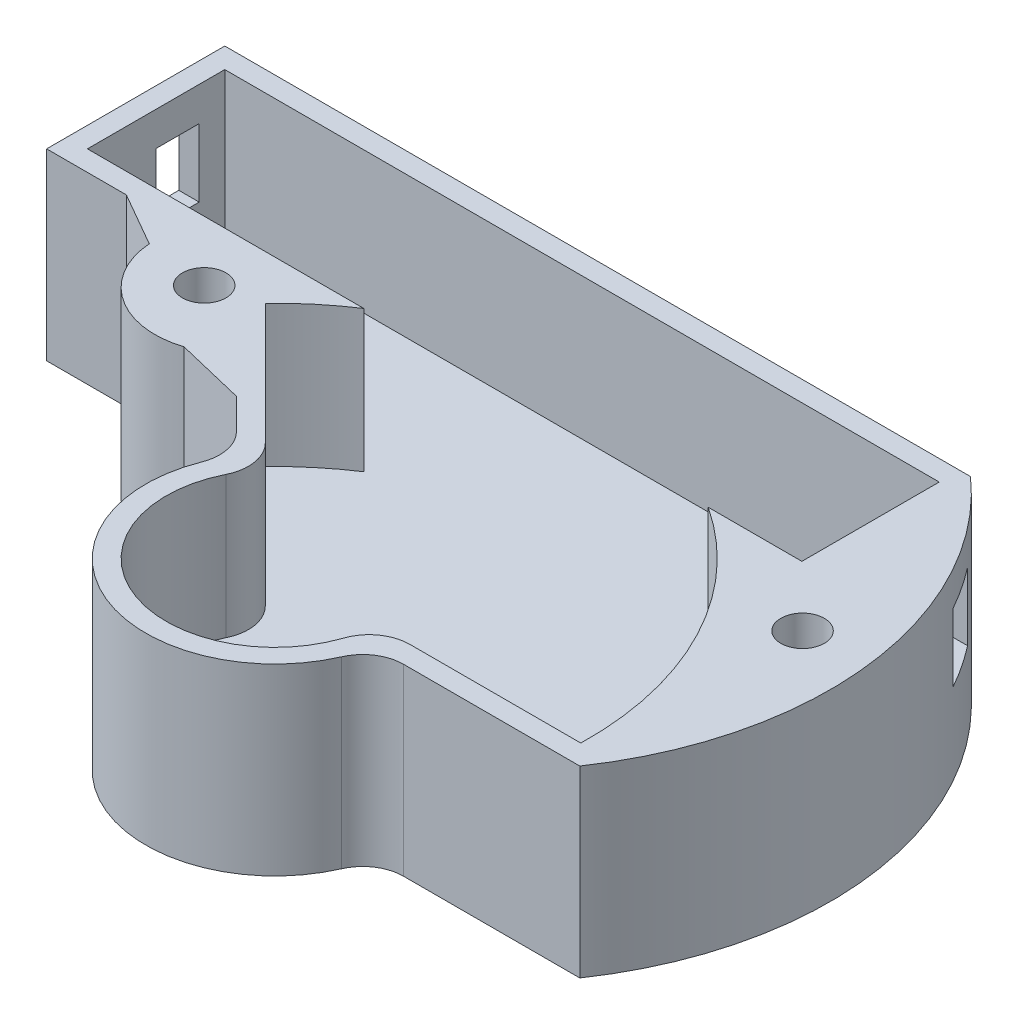
SolidWorks part; units mm, degrees
ref_plane "Alzado" through (0, 0, 0) normal (0, 0, 1) x (1, 0, 0)
ref_plane "Planta" through (0, 0, 0) normal (0, 1, 0) x (1, 0, 0)
ref_plane "Vista lateral" through (0, 0, 0) normal (1, 0, 0) x (0, 0, -1)
sketch "Croquis1" plane through (0, 0, 0) normal (0, 1, 0) x (1, 0, 0)
  line L0 (-35, 32.5) -> (35, -32.5) construction
  line L1 (-35, 32.5) -> (35, 32.5)
  line L2 (-35, 32.5) -> (-35, -32.5)
  line L3 (-35, -32.5) -> (35, -32.5)
  line L4 (35, 32.5) -> (35, -32.5)
  dimension "D1" = 70
  dimension "D2" = 65
extrude "Extruir1" add sketch "Croquis1" along normal blind 3.5
sketch "Croquis2" plane through (0, 3.5, 0) normal (0, 1, 0) x (1, 0, 0)
  line L0 (0, 32.5) -> (0, -32.5) construction
  line L1 (35, 32.5) -> (-35, 32.5) construction
  line L2 (-35, -32.5) -> (35, -32.5) construction
  circle A0 centre (0, -17.5) radius 3.1
  dimension "D1" = 6.2
  dimension "D2" = 15
extrude "Extruir2" cut sketch "Croquis2" against normal blind 5
sketch "Croquis3" plane through (0, 3.5, 0) normal (0, 1, 0) x (1, 0, 0)
  line L0 (0, -32.5) -> (0, 32.5) construction
  line L1 (-35, -32.5) -> (35, -32.5) construction
  line L2 (35, 32.5) -> (-35, 32.5) construction
  line L3 (-32.9868, -32.5) -> (-32.9868, 32.5) construction
  line L4 (-32.9868, 1.7) -> (-12.6633, 1.7)
  line L5 (18.8496, -32.5) -> (18.8496, 32.5) construction
  line L6 (-32.9868, 3.5) -> (18.8496, 3.5) construction
  line L7 (-32.9868, 2) -> (0, 2) construction
  line L8 (-32.9868, 11.5) -> (18.8496, 11.5) construction
  line L9 (0, -17.5) -> (-14.8492, -2.6508) construction
  line L10 (0, -17.5) -> (14.8492, -2.6508) construction
  line L11 (0, 2) -> (18.8496, 2) construction
  line L12 (-32.9868, 2) -> (18.8496, 2) construction
  line L13 (-32.9868, 11.8) -> (18.8496, 11.8)
  line L14 (-5.3033, -12.1967) -> (-16.2635, -1.2365) construction
  line L15 (12.6633, 1.7) -> (18.8496, 1.7)
  line L16 (-32.9868, 1.7) -> (18.8496, 1.7) construction
  line L17 (7.9844, -18) -> (22.9946, -18)
  line L18 (-5.9993, -12.2078) -> (-16.6132, -1.5939)
  line L19 (0, -17.5) -> (23, -17.5) construction
  line L20 (7.5, -17.5) -> (23, -17.5) construction
  line L21 (-5.6569, -12.5503) -> (-16.617, -1.5901) construction
  line L22 (7.5, -18) -> (23, -18) construction
  line L23 (-32.9868, 11.8) -> (-32.9868, 1.7)
  line L24 (18.8496, 11.8) -> (18.8496, 1.7)
  line L25 (-34.4868, 13.3) -> (20.3496, 13.3)
  line L26 (20.3496, 13.3) -> (20.3496, 0.2)
  line L27 (16.9399, 0.2) -> (20.3496, 0.2)
  line L28 (9.2871, -19.5) -> (24.4182, -19.5)
  line L29 (-7.9812, -12.3473) -> (-18.6805, -1.6479)
  line L30 (-34.4868, 0.2) -> (-16.9399, 0.2)
  line L31 (-34.4868, 13.3) -> (-34.4868, 0.2)
  circle A0 centre (0, -17.5) radius 21 construction
  circle A1 centre (0, -17.5) radius 7.5 construction
  arc A2 (-12.6633, 1.7) -> (-16.6132, -1.5939) centre (0, -17.5) ccw
  circle A3 centre (0, -17.5) radius 23 construction
  arc A4 (-5.9993, -12.2078) -> (7.9844, -18) centre (0, -17.5) ccw
  arc A5 (22.9946, -18) -> (12.6633, 1.7) centre (0, -17.5) ccw
  arc A6 (24.4182, -19.5) -> (16.9399, 0.2) centre (0, -17.5) ccw
  arc A7 (-7.9812, -12.3473) -> (9.2871, -19.5) centre (0, -17.5) ccw
  arc A8 (-16.9399, 0.2) -> (-18.6805, -1.6479) centre (0, -17.5) ccw
  dimension "D3" = 42
  dimension "D8" = 15
  dimension "D9" = 46
  dimension "D14" = 0.5
  dimension "D2" = 51.8364
  dimension "D6" = 90
  dimension "D7" = 45
  dimension "D1" = 32.9868
  dimension "D4" = 1.5
  dimension "D5" = 9.5
  dimension "D10" = 1.8
  dimension "D11" = 0.3
  dimension "D12" = 0.5
  dimension "D13" = 0.5
  dimension "D15" = 1.5
extrude "Extruir3" add sketch "Croquis3" along normal blind 10
sketch "Croquis4" plane through (0, 3.5, 0) normal (0, 1, 0) x (1, 0, 0)
  line L0 (-34.4868, 0.2) -> (-16.9399, 0.2) construction
  line L1 (-34.4868, 13.3) -> (-34.4868, 0.2) construction
  line L2 (20.3496, 13.3) -> (-34.4868, 13.3) construction
  line L3 (20.3496, 0.2) -> (20.3496, 13.3) construction
  line L4 (16.9399, 0.2) -> (20.3496, 0.2) construction
  line L5 (9.2871, -19.5) -> (24.4182, -19.5) construction
  line L6 (-18.6805, -1.6479) -> (-7.9812, -12.3473) construction
  line L7 (-34.4868, 0.2) -> (-16.9399, 0.2)
  line L8 (-34.4868, 13.3) -> (-34.4868, 0.2)
  line L9 (20.3496, 13.3) -> (-34.4868, 13.3)
  line L10 (20.3496, 0.2) -> (20.3496, 13.3)
  line L11 (16.9399, 0.2) -> (20.3496, 0.2)
  line L12 (9.2871, -19.5) -> (24.4182, -19.5)
  line L13 (-18.6805, -1.6479) -> (-7.9812, -12.3473)
  arc A0 (-16.9399, 0.2) -> (-18.6805, -1.6479) centre (0, -17.5) ccw construction
  arc A1 (24.4182, -19.5) -> (16.9399, 0.2) centre (0, -17.5) ccw construction
  arc A2 (-7.9812, -12.3473) -> (9.2871, -19.5) centre (0, -17.5) ccw construction
  arc A3 (-16.9399, 0.2) -> (-18.6805, -1.6479) centre (0, -17.5) ccw
  arc A4 (24.4182, -19.5) -> (16.9399, 0.2) centre (0, -17.5) ccw
  arc A5 (-7.9812, -12.3473) -> (9.2871, -19.5) centre (0, -17.5) ccw
extrude "Extruir4" cut sketch "Croquis4" against normal blind 10 flip side to cut
fillet "Redondeo1" radius 3 4 edges at (9.2871, 6.75, 19.5) (-7.9812, 6.75, 12.3473) (7.9844, 8.5, 18) (-5.9993, 8.5, 12.2078)
sketch "Croquis5" plane through (0, 0, 0) normal (0, -1, 0) x (1, 0, 0)
  line L0 (-18.6805, 1.6479) -> (-9.5151, 10.8133) construction
  line L1 (-34.4868, -0.2) -> (-16.9399, -0.2) construction
  line L2 (-18.6805, 1.6479) -> (-14.4379, 5.8906)
  line L3 (-24.3889, -0.2) -> (-16.9399, -0.2)
  line L4 (20.3496, -0.2) -> (20.3496, -13.3) construction
  line L5 (16.9399, -0.2) -> (20.3496, -0.2) construction
  line L6 (20.3496, -0.2) -> (20.3496, -13.3)
  line L7 (16.9399, -0.2) -> (20.3496, -0.2)
  arc A0 (-14.4379, 5.8906) -> (-24.3889, -0.2) centre (-18.6805, 1.6479) ccw
  arc A1 (-18.6805, 1.6479) -> (-16.9399, -0.2) centre (0, 17.5) ccw construction
  arc A2 (-18.6805, 1.6479) -> (-16.9399, -0.2) centre (0, 17.5) ccw
  arc A3 (24.4182, 19.5) -> (20.3496, -13.3) centre (3.7676, 5.4092) cw
  arc A4 (16.9399, -0.2) -> (24.4182, 19.5) centre (0, 17.5) ccw construction
  arc A5 (16.9399, -0.2) -> (24.4182, 19.5) centre (0, 17.5) ccw
  dimension "D1" = 12
  dimension "D2" = 25
extrude "Extruir5" add sketch "Croquis5" against normal up to surface (13.5 mm away) up to face at (-1.8238, 13.5, 5.5521)
chamfer "Chaflán1" distance 5 angle 45 2 edges at (-14.4379, 6.75, 5.8906) (-24.3889, 6.75, -0.2) first distance on face at (-11.9765, 6.75, 8.3519) first distance on face at (-29.4378, 6.75, -0.2)
sketch "Croquis6" plane through (0, 13.5, 0) normal (0, 1, 0) x (1, 0, 0)
  line L7 (-34.4868, 13.3) -> (-34.4868, 0.2)
  line L8 (-34.4868, 0.2) -> (-28.6257, 0.2)
  line L9 (-28.6257, 0.2) -> (-24.6654, -2.0731)
  line L10 (-16.83, -7.3554) -> (-11.7523, -8.5761)
  line L11 (-11.7523, -8.5761) -> (-9.5151, -10.8133)
  line L12 (11.4564, -19.5) -> (24.4182, -19.5)
  line L13 (20.3496, 13.3) -> (-34.4868, 13.3)
  line L14 (-34.4868, 13.3) -> (-34.4868, 0.2)
  line L15 (-34.4868, 0.2) -> (-28.6257, 0.2)
  line L16 (-28.6257, 0.2) -> (-24.6654, -2.0731)
  line L17 (-16.83, -7.3554) -> (-11.7523, -8.5761)
  line L18 (-11.7523, -8.5761) -> (-9.5151, -10.8133)
  line L19 (11.4564, -19.5) -> (24.4182, -19.5)
  line L20 (20.3496, 13.3) -> (-34.4868, 13.3)
  arc A5 (-24.6654, -2.0731) -> (-16.83, -7.3554) centre (-18.6805, -1.6479) ccw
  arc A6 (-8.8437, -14.0303) -> (-9.5151, -10.8133) centre (-11.6365, -12.9346) ccw
  arc A7 (-8.8437, -14.0303) -> (8.7069, -21.3) centre (0, -17.5) ccw
  arc A8 (11.4564, -19.5) -> (8.7069, -21.3) centre (11.4564, -22.5) ccw
  arc A9 (24.4182, -19.5) -> (20.3496, 13.3) centre (3.7676, -5.4092) ccw
  arc A10 (-24.6654, -2.0731) -> (-16.83, -7.3554) centre (-18.6805, -1.6479) ccw
  arc A11 (-8.8437, -14.0303) -> (-9.5151, -10.8133) centre (-11.6365, -12.9346) ccw
  arc A12 (-8.8437, -14.0303) -> (8.7069, -21.3) centre (0, -17.5) ccw
  arc A13 (11.4564, -19.5) -> (8.7069, -21.3) centre (11.4564, -22.5) ccw
  arc A14 (24.4182, -19.5) -> (20.3496, 13.3) centre (3.7676, -5.4092) ccw
  dimension "D1" = 0
extrude "Extruir6" add sketch "Croquis6" along normal blind 3.5 separate body
sketch "Croquis7" plane through (0, 17, 0) normal (0, 1, 0) x (1, 0, 0)
  line L0 (20.3496, 13.3) -> (-34.4868, 13.3) construction
  circle A0 centre (-20, -2.7) radius 1.6
  circle A1 centre (24, -2.7) radius 1.6
  dimension "D1" = 3.2
  dimension "D2" = 16
  dimension "D3" = 20
  dimension "D4" = 24
extrude "Extruir7" cut sketch "Croquis7" against normal through all
sketch "Croquis8" plane through (0, 17, 0) normal (0, 1, 0) x (1, 0, 0)
  circle A0 centre (0, -17.5) radius 3.1 construction
  circle A1 centre (0, -17.5) radius 3.1
extrude "Extruir8" cut sketch "Croquis8" against normal blind 5
sketch "Croquis9" plane through (0, 13.5, 0) normal (0, 1, 0) x (1, 0, 0)
  line L0 (18.8496, 1.7) -> (18.8496, 11.8) construction
  line L1 (18.8496, 1.7) -> (18.8496, 11.8)
  line L2 (19.5496, 1.7) -> (19.5496, 11.8)
  line L3 (18.8496, 11.8) -> (19.5496, 11.8)
  line L4 (18.8496, 1.7) -> (19.5496, 1.7)
  dimension "D1" = 0.7
extrude "Extruir9" cut sketch "Croquis9" against normal up to surface (10 mm away) up to face at (-1.614, 3.5, 4.797)
sketch "Croquis10" plane through (19.5496, 0, 0) normal (-1, 0, 0) x (0, 0, 1)
  line L0 (-5.175, 13.5) -> (-5.175, 3.5) construction
  line L1 (-11.5, 13.5) -> (-11.5, 3.5) construction
  line L3 (-1.7, 13.5) -> (-11.8, 13.5) construction
  line L4 (-11.8, 3.5) -> (-11.8, 13.5) construction
  line L5 (-5.175, 13.5) -> (-11.5, 3.5) construction
  line L6 (-11.8, 3.5) -> (-1.7, 3.5) construction
  line L7 (-8.3375, 8.5) -> (-11.5, 13.5) construction
  line L8 (19.5, 13.5) -> (-13.3, 13.5) construction
  line L10 (-6.7562, 11) -> (-9.9187, 11)
  line L11 (-6.7562, 11) -> (-6.7562, 6)
  line L12 (-6.7562, 6) -> (-9.9187, 6)
  line L13 (-9.9187, 11) -> (-9.9187, 6)
  dimension "D1" = 6.625
  dimension "D2" = 5
  dimension "D3" = 3.1625
  dimension "D4" = 0.3
extrude "Extruir10" cut sketch "Croquis10" against normal blind 10 and the other way through all
delete or keep bodies "Sólido-Eliminar1" type delete bodies bodies 109
sketch "Croquis11" plane through (0, 3.5, 0) normal (0, 1, 0) x (1, 0, 0)
  line L7 (-32.9868, 11.8) -> (-32.9868, 1.7)
  line L8 (-32.9868, 1.7) -> (-12.6633, 1.7)
  line L9 (-16.6132, -1.5939) -> (-7.7275, -10.4796)
  line L10 (10.4283, -18) -> (22.9946, -18)
  line L11 (12.6633, 1.7) -> (19.5496, 1.7)
  line L12 (19.5496, 1.7) -> (19.5496, 11.8)
  line L13 (19.5496, 11.8) -> (-32.9868, 11.8)
  line L14 (-32.9868, 11.8) -> (-32.9868, 1.7)
  line L15 (-32.9868, 1.7) -> (-12.6633, 1.7)
  line L16 (-16.6132, -1.5939) -> (-7.7275, -10.4796)
  line L17 (10.4283, -18) -> (22.9946, -18)
  line L18 (12.6633, 1.7) -> (19.5496, 1.7)
  line L19 (19.5496, 1.7) -> (19.5496, 11.8)
  line L20 (19.5496, 11.8) -> (-32.9868, 11.8)
  arc A5 (-12.6633, 1.7) -> (-16.6132, -1.5939) centre (0, -17.5) ccw
  arc A6 (-7.1628, -13.937) -> (-7.7275, -10.4796) centre (-9.8488, -12.6009) ccw
  arc A7 (-7.1628, -13.937) -> (7.5842, -20.0455) centre (0, -17.5) ccw
  arc A8 (10.4283, -18) -> (7.5842, -20.0455) centre (10.4283, -21) ccw
  arc A9 (22.9946, -18) -> (12.6633, 1.7) centre (0, -17.5) ccw
  arc A10 (-12.6633, 1.7) -> (-16.6132, -1.5939) centre (0, -17.5) ccw
  arc A11 (-7.1628, -13.937) -> (-7.7275, -10.4796) centre (-9.8488, -12.6009) ccw
  arc A12 (-7.1628, -13.937) -> (7.5842, -20.0455) centre (0, -17.5) ccw
  arc A13 (10.4283, -18) -> (7.5842, -20.0455) centre (10.4283, -21) ccw
  arc A14 (22.9946, -18) -> (12.6633, 1.7) centre (0, -17.5) ccw
  dimension "D1" = 0
extrude "Extruir11" cut sketch "Croquis11" against normal blind 0.4
move or copy body "Sólido-Mover/Copiar1" [suppressed] bodies to move or copy 112
